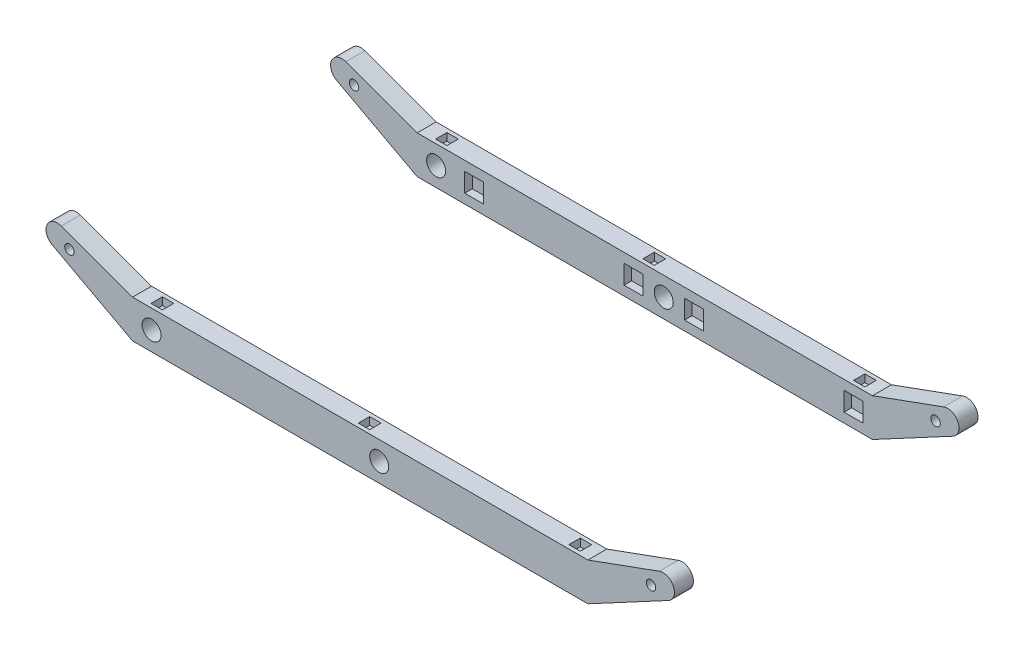
SolidWorks part; units mm, degrees
ref_plane "Front Plane" through (0, 0, 0) normal (0, 0, 1) x (1, 0, 0)
ref_plane "Top Plane" through (0, 0, 0) normal (0, 1, 0) x (1, 0, 0)
ref_plane "Right Plane" through (0, 0, 0) normal (1, 0, 0) x (0, 0, -1)
sketch "Sketch1" plane through (0, 0, 0) normal (1, 0, 0) x (0, 0, -1)
  line L1 (-25, 50) -> (25, 50)
  line L2 (-25, 50) -> (-25, -50)
  line L3 (-25, -50) -> (25, -50)
  line L4 (25, 50) -> (25, -50)
  line L5 (-25, 50) -> (25, -50) construction
  line L6 (-25, -50) -> (25, 50) construction
  point P0 (0, 0)
  dimension "D1" = 50
  dimension "D2" = 100
extrude "Boss-Extrude3" add sketch "Sketch1" along normal blind 600 and the other way blind 600
sketch "Sketch3" plane through (0, 0, 25) normal (0, 0, 1) x (1, 0, 0)
  line L3 (600, 50) -> (1680.9398, 50) construction
  line L4 (600, 50) -> (787.9385, 118.404)
  line L6 (812.3659, 63.7689) -> (600, -50)
  line L7 (600, -50) -> (600, 50)
  arc A2 (812.3659, 63.7689) -> (787.9385, 118.404) centre (798.1991, 90.2133) ccw
  dimension "D3" = 200
  dimension "D2" = 30
  dimension "D1" = 20
extrude "Boss-Extrude4" add sketch "Sketch3" against normal blind 50
mirror "Mirror1" about plane through (0, 0, 0) normal (1, 0, 0) of "Boss-Extrude4"
sketch "Sketch4" plane through (0, 0, 25) normal (0, 0, 1) x (1, 0, 0)
  line L0 (766.3206, 75.7943) -> (754.9587, 106.4003) construction
  line L1 (787.9385, 118.404) -> (600, 50) construction
  line L2 (766.3206, 75.7943) -> (777.6826, 45.1883) construction
  line L3 (600, -50) -> (812.3659, 63.7689) construction
  line L9 (0, 0) -> (0, 50) construction
  line L10 (-600, 50) -> (600, 50) construction
  line L11 (-766.3206, 75.7943) -> (-760.6651, 86.9418) construction
  line L12 (-766.3206, 75.7943) -> (-771.2166, 87.2956) construction
  circle A1 centre (-550, 0) radius 25
  circle A2 centre (50, 0) radius 25
  circle A3 centre (766.3206, 75.7943) radius 12.5
  circle A4 centre (-766.3206, 75.7943) radius 12.5
  dimension "D1" = 180
  dimension "D2" = 25
extrude "Cut-Extrude1" cut sketch "Sketch4" against normal through all
sketch "Sketch5" plane through (0, 0, -25) normal (0, 0, -1) x (-1, 0, 0)
  line L0 (29.6577, 0) -> (449.6577, 0) construction
  line L1 (-574.9923, 25) -> (-524.9923, -25) construction
  line L2 (-574.9923, -25) -> (-524.9923, 25) construction
  line L3 (-549.9923, 0) -> (29.6577, 0) construction
  line L5 (424.6577, 25) -> (474.6577, 25)
  line L6 (424.6577, 25) -> (424.6577, -25)
  line L7 (424.6577, -25) -> (474.6577, -25)
  line L8 (474.6577, 25) -> (474.6577, -25)
  line L9 (424.6577, 25) -> (474.6577, -25) construction
  line L10 (424.6577, -25) -> (474.6577, 25) construction
  line L11 (4.6577, 25) -> (54.6577, 25)
  line L12 (4.6577, 25) -> (4.6577, -25)
  line L13 (4.6577, -25) -> (54.6577, -25)
  line L14 (54.6577, 25) -> (54.6577, -25)
  line L15 (4.6577, 25) -> (54.6577, -25) construction
  line L16 (4.6577, -25) -> (54.6577, 25) construction
  line L18 (-524.9923, 25) -> (-524.9923, -25)
  line L19 (-524.9923, -25) -> (-574.9923, -25)
  line L20 (-574.9923, 25) -> (-574.9923, -25)
  line L21 (-524.9923, 25) -> (-574.9923, 25)
  line L22 (-104.6577, 25) -> (-104.6577, -25)
  line L23 (-104.6577, -25) -> (-154.6577, -25)
  line L24 (-154.6577, 25) -> (-154.6577, -25)
  line L25 (-104.6577, 25) -> (-154.6577, 25)
  point P5 (449.6577, 0)
  point P16 (29.6577, 0)
  dimension "D1" = 50
  dimension "D2" = 50
  dimension "D3" = 50
  dimension "D4" = 50
  dimension "D5" = 420
  dimension "D6" = 579.65
extrude "Cut-Extrude2" cut sketch "Sketch5" against normal blind 20
sketch "Sketch7" plane through (0, 50, 0) normal (0, 1, 0) x (1, 0, 0)
  line L0 (-600, 25) -> (-546.5, 25) construction
  line L1 (-600, 25) -> (600, 25) construction
  line L2 (-546.5, 25) -> (-546.5, -25) construction
  line L3 (-600, -25) -> (600, -25) construction
  line L4 (0, -25) -> (0, 25) construction
  line L5 (-561.5, 15) -> (-531.5, 15)
  line L6 (-561.5, 15) -> (-561.5, -15)
  line L7 (-561.5, -15) -> (-531.5, -15)
  line L8 (-531.5, 15) -> (-531.5, -15)
  line L9 (-561.5, 15) -> (-531.5, -15) construction
  line L10 (-561.5, -15) -> (-531.5, 15) construction
  line L11 (600, 25) -> (555, 25) construction
  line L12 (-15, 15) -> (15, 15)
  line L13 (-15, 15) -> (-15, -15)
  line L14 (-15, -15) -> (15, -15)
  line L15 (15, 15) -> (15, -15)
  line L16 (-15, 15) -> (15, -15) construction
  line L17 (-15, -15) -> (15, 15) construction
  line L18 (555, 25) -> (555, -25) construction
  line L20 (540, 15) -> (570, 15)
  line L21 (540, 15) -> (540, -15)
  line L22 (540, -15) -> (570, -15)
  line L23 (570, 15) -> (570, -15)
  line L24 (540, 15) -> (570, -15) construction
  line L25 (540, -15) -> (570, 15) construction
  point P5 (-546.5, 0)
  point P15 (0, 0)
  point P23 (555, 0)
  dimension "D1" = 53.5
  dimension "D2" = 30
  dimension "D3" = 30
  dimension "D4" = 30
  dimension "D5" = 30
  dimension "D6" = 45
  dimension "D7" = 30
  dimension "D8" = 30
extrude "Cut-Extrude3" cut sketch "Sketch7" against normal blind 20
ref_plane "Plane3" through (0, 0, -375) normal (0, 0, -1) x (-1, 0, 0)
mirror "Mirror4" about plane through (0, 0, -375) normal (0, 0, -1) of bodies 108
